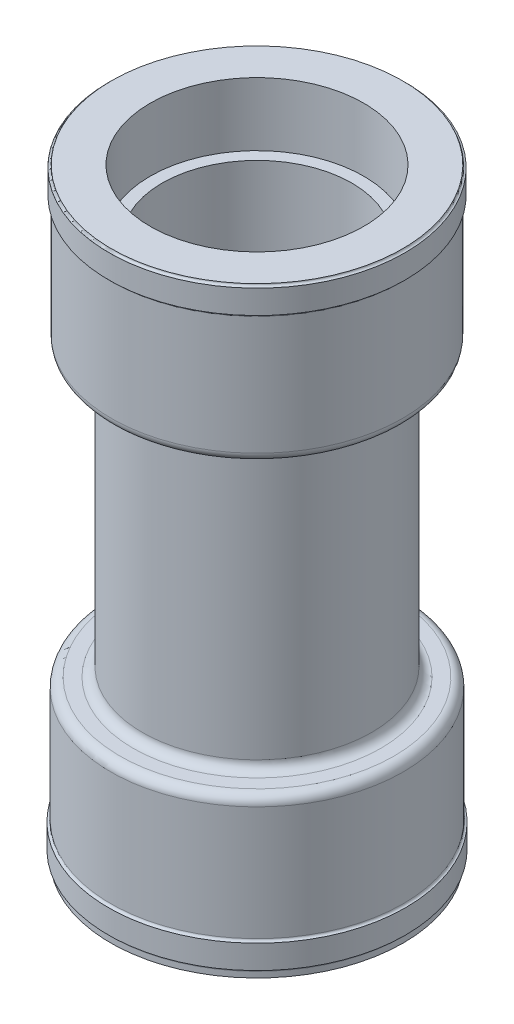
SolidWorks part; units mm, degrees
ref_plane "Front Plane" through (0, 0, 0) normal (0, 0, 1) x (1, 0, 0)
ref_plane "Top Plane" through (0, 0, 0) normal (0, 1, 0) x (1, 0, 0)
ref_plane "Right Plane" through (0, 0, 0) normal (1, 0, 0) x (0, 0, -1)
sketch "Sketch1" plane through (0, 0, 0) normal (0, 0, 1) x (1, 0, 0)
  line L0 (-19.9139, -39.6278) -> (-19.9139, 60.3722)
  line L1 (-19.9139, 60.3722) -> (-14.7139, 60.3722)
  line L2 (-14.7139, 60.3722) -> (-14.7139, 87.9722)
  line L3 (-14.7139, 87.9722) -> (2.1946, 87.9722)
  line L4 (2.1946, 87.9722) -> (2.1946, 86.9722)
  line L5 (2.1946, 86.9722) -> (3.2148, 86.9722)
  line L6 (3.2148, 86.9722) -> (3.2148, 76.6285)
  line L7 (3.2148, 76.6285) -> (2.2107, 76.6285)
  line L8 (2.2107, 76.6285) -> (2.2107, 19.8954)
  line L9 (2.2107, 19.8954) -> (-11.3139, 19.8954)
  line L10 (-11.3139, 19.8954) -> (-11.3139, -39.6278)
  line L15 (-19.9139, -39.6278) -> (-19.9139, -139.6278)
  line L16 (-19.9139, -139.6278) -> (-14.7168, -139.6278)
  line L17 (-14.7168, -139.6278) -> (-14.7168, -174.1743)
  line L18 (-14.7168, -174.1743) -> (2.5102, -174.1743)
  line L19 (2.5102, -174.1743) -> (2.5102, -170.6715)
  line L20 (2.5102, -170.6715) -> (3.506, -170.6715)
  line L21 (3.506, -170.6715) -> (3.506, -160.3211)
  line L22 (3.506, -160.3211) -> (2.5015, -160.3211)
  line L23 (2.5015, -160.3211) -> (2.5015, -105.5373)
  line L24 (2.5015, -105.5373) -> (-11.3139, -105.5373)
  line L25 (-11.3139, -105.5373) -> (-11.3139, -39.6278)
  line L26 (-61.3139, 87.9722) -> (-61.3139, -174.1743)
  dimension "D1" = 41.4
revolve "Revolve2" add sketch "Sketch1" angle 360 about L26 region at (-17.282, 10.3722, 0)
fillet "Fillet6" radius 1 4 edges at (-125.1294, -160.3211, 0) (-125.138, -170.6715, 0) (-124.8385, 76.6285, 0) (-124.8224, 86.9722, 0)
fillet "Fillet7" radius 4 4 edges at (-111.3139, -105.5373, 0) (-125.1294, -105.5373, 0) (-111.3139, 19.8954, 0) (-124.8385, 19.8954, 0)
